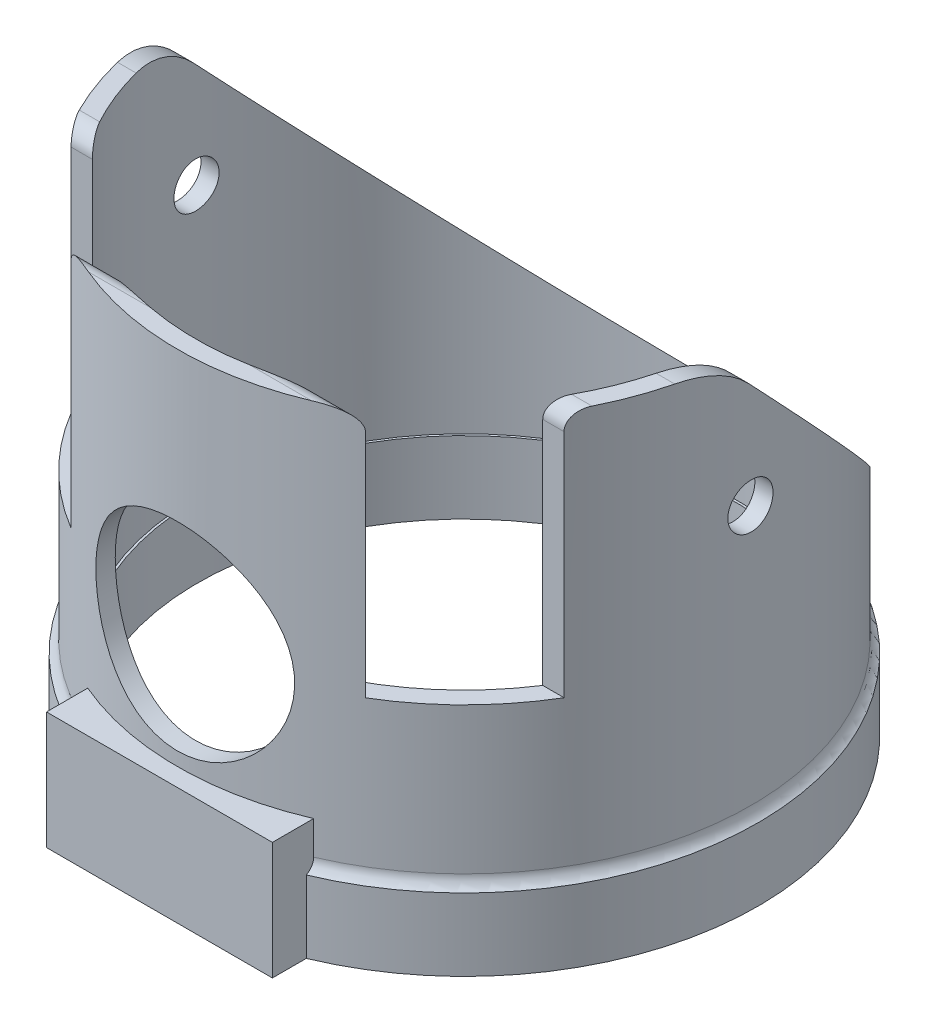
SolidWorks part; units mm, degrees
ref_plane "Спереди" through (0, 0, 0) normal (0, 0, 1) x (1, 0, 0)
ref_plane "Сверху" through (0, 0, 0) normal (0, 1, 0) x (1, 0, 0)
ref_plane "Справа" through (0, 0, 0) normal (1, 0, 0) x (0, 0, -1)
sketch "Эскиз1" plane through (0, 0, 0) normal (0, 1, 0) x (1, 0, 0)
  circle A0 centre (0, 0) radius 32.5
  circle A1 centre (0, 0) radius 29.5
  dimension "D1" = 65
  dimension "D2" = 59
extrude "lower part" add sketch "Эскиз1" along normal blind 8
sketch "Эскиз2" plane through (0, 0, 0) normal (0, -1, 0) x (1, 0, 0)
  circle A0 centre (0, 0) radius 31.5
  circle A1 centre (0, 0) radius 30
  dimension "D1" = 63
  dimension "D2" = 60
extrude "slot" cut sketch "Эскиз2" against normal blind 3
sketch "Эскиз3" plane through (0, 8, 0) normal (0, 1, 0) x (1, 0, 0)
  circle A0 centre (0, 0) radius 31.75
  circle A1 centre (0, 0) radius 29.75
  dimension "D1" = 63.5
  dimension "D2" = 59.5
extrude "higher part" add sketch "Эскиз3" along normal blind 45
sketch "Эскиз4" plane through (0, 0, 0) normal (1, 0, 0) x (0, 0, -1)
  line L0 (31.75, 53) -> (31.75, 16)
  line L1 (31.75, 8) -> (31.75, 53) construction
  line L2 (31.75, 16) -> (-3.25, 53)
  line L3 (29.75, 53) -> (-29.75, 53) construction
  line L4 (-3.25, 53) -> (31.75, 53)
  dimension "D1" = 35
  dimension "D2" = 37
extrude "triangle" cut sketch "Эскиз4" against normal through all and the other way through all
ref_plane "tube start" through (0, 0, 12) normal (0, 0, 1) x (1, 0, 0)
sketch "Эскиз7" plane through (0, 0, 0) normal (1, 0, 0) x (0, 0, -1)
  line L0 (-3.25, 53) -> (-31.75, 53) construction
  line L1 (-16.25, 53) -> (-27.25, 53)
  line L2 (-16.25, 53) -> (-16.25, 25.5)
  line L3 (-16.25, 25.5) -> (-27.25, 25.5)
  line L4 (-27.25, 53) -> (-27.25, 25.5)
  line L5 (-32.5, 0) -> (32.5, 0) construction
  dimension "D1" = 11
  dimension "D2" = 25.5
  dimension "D3" = 4.5
extrude "key slot" cut sketch "Эскиз7" against normal up to next and the other way up to next
sketch "Эскиз5" plane through (0, 0, 0) normal (0, 0, 1) x (1, 0, 0)
  line L0 (-32.5, 0) -> (32.5, 0) construction
  circle A0 centre (0, 25.5) radius 11
  dimension "D2" = 22
  dimension "D1" = 25.5
extrude "hole" cut sketch "Эскиз5" along normal through all
sketch "Эскиз9" plane through (0, 0, 0) normal (1, 0, 0) x (0, 0, -1)
  circle A0 centre (0, 38) radius 2.5
  dimension "D1" = 5
  dimension "D2" = 38
extrude "small hole" cut sketch "Эскиз9" against normal through all and the other way through all
sketch "Эскиз11" plane through (0, 0, 0) normal (0, 1, 0) x (1, 0, 0)
  line L0 (-12.5, -29.1858) -> (12.5, -29.1858) construction
  line L1 (12.5, -29.1858) -> (12.5, -33.75)
  line L2 (12.5, -33.75) -> (-12.5, -33.75)
  line L3 (-12.5, -33.75) -> (-12.5, -29.1858)
  line L4 (0, 0) -> (0, -31.75) construction
  circle A0 centre (0, 0) radius 31.75 construction
  arc A1 (-16.2942, -27.25) -> (16.2942, -27.25) centre (0, 0) ccw construction
  arc A2 (-12.5, -29.1858) -> (12.5, -29.1858) centre (0, 0) ccw
  dimension "D1" = 25
  dimension "D2" = 2
extrude "support" add sketch "Эскиз11" along normal blind 13
fillet "Скругление1" radius 1.5 1 edges at (0, 8, -31.75)
fillet "Скругление2" radius 10 2 edges at (-30.5776, 53, 3.25) (30.5776, 53, 3.25)
fillet "Скругление3" radius 2 4 edges at (-26.0981, 53, 16.25) (-14.1158, 53, 27.25) (14.1158, 53, 27.25) (26.0981, 53, 16.25)
